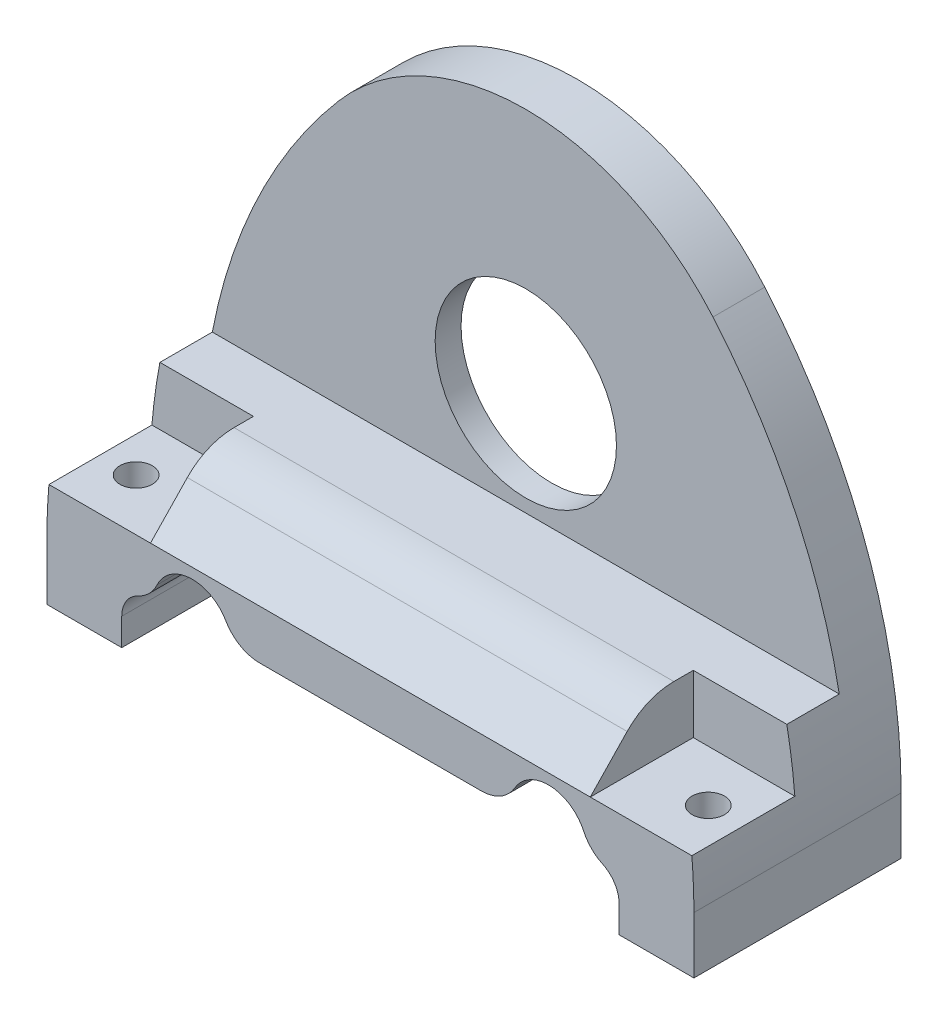
SolidWorks part; units mm, degrees
ref_plane "Plano frontal" through (0, 0, 0) normal (0, 0, 1) x (1, 0, 0)
ref_plane "Plano superior" through (0, 0, 0) normal (0, 1, 0) x (1, 0, 0)
ref_plane "Plano direito" through (0, 0, 0) normal (1, 0, 0) x (0, 0, -1)
sketch "Esboço1" plane through (0, 0, 0) normal (0, 0, 1) x (1, 0, 0)
  line L0 (0, 0) -> (24.98, 0) construction
  line L1 (0, 0) -> (-24.98, 0) construction
  line L2 (0, 0) -> (0, -20.6) construction
  line L3 (-24.98, -20.6) -> (24.98, -20.6) construction
  line L4 (-24.98, -20.6) -> (-24.98, 0)
  line L5 (-24.98, 0) -> (-14.4516, 12.335)
  line L6 (24.98, -20.6) -> (24.98, 0)
  line L7 (24.98, 0) -> (14.4516, 12.335)
  line L11 (18.98, -20.6) -> (24.98, -20.6)
  line L14 (-18.98, -20.6) -> (-24.98, -20.6)
  line L16 (18.98, -20.6) -> (-18.98, -20.6)
  circle A0 centre (0, 0) radius 14.95
  arc A1 (14.4516, 12.335) -> (-14.4516, 12.335) centre (0, 0) ccw
  dimension "D1" = 37.96
  dimension "D2" = 29.9
  dimension "D3" = 38
  dimension "D5" = 20.6
  dimension "D8" = 6
  dimension "D9" = 6
extrude "Ressalto-extrusão1" add sketch "Esboço1" along normal blind 2
sketch "Esboço2" plane through (0, 0, 2) normal (0, 0, 1) x (1, 0, 0)
  line L5 (24.98, 0) -> (14.4516, 12.335)
  line L6 (-14.4516, 12.335) -> (-24.98, 0)
  line L7 (-24.98, 0) -> (-24.98, -20.6)
  line L8 (-24.98, -20.6) -> (24.98, -20.6)
  line L9 (24.98, -20.6) -> (24.98, 0)
  line L10 (24.98, 0) -> (14.4516, 12.335)
  line L11 (-14.4516, 12.335) -> (-24.98, 0)
  line L12 (-24.98, 0) -> (-24.98, -20.6)
  line L13 (-24.98, -20.6) -> (24.98, -20.6)
  line L14 (24.98, -20.6) -> (24.98, 0)
  circle A0 centre (0, 0) radius 7
  arc A1 (14.4516, 12.335) -> (-14.4516, 12.335) centre (0, 0) ccw
  arc A2 (14.4516, 12.335) -> (-14.4516, 12.335) centre (0, 0) ccw
  dimension "D2" = 14
  dimension "D1" = 0
extrude "Ressalto-extrusão2" add sketch "Esboço2" along normal blind 2
sketch "Esboço3" plane through (0, -20.6, 0) normal (0, -1, 0) x (1, 0, 0)
  line L0 (24.98, 4) -> (24.98, 0) construction
  line L1 (-24.98, 4) -> (24.98, 4)
  line L2 (-24.98, 4) -> (-24.98, 16)
  line L3 (-24.98, 16) -> (24.98, 16)
  line L4 (24.98, 4) -> (24.98, 16)
  dimension "D1" = 12
extrude "Ressalto-extrusão3" add sketch "Esboço3" against normal blind 8.1
chamfer "Chanfro1" distance 12 distance2 12.5 1 edges
fillet "Filete1" radius 44 2 edges at (-24.98, 0, 2) (24.98, 0, 2)
sketch "Esboço4" plane through (0, 0, 16) normal (0, 0, 1) x (1, 0, 0)
  line L1 (17, -16.5) -> (-17, -16.5) construction
  line L3 (17, -16.5) -> (-17, -16.5)
  line L4 (19, -18.5) -> (19, -20.6)
  line L5 (-19, -18.5) -> (-19, -20.6)
  line L8 (24.8221, -12.5) -> (-24.8221, -12.5)
  line L9 (-24.98, -16.2247) -> (-24.98, -20.6)
  line L10 (-24.98, -20.6) -> (24.98, -20.6)
  line L11 (24.98, -20.6) -> (24.98, -16.2247)
  line L14 (-19, -20.6) -> (19, -20.6)
  arc A0 (-17, -16.5) -> (-17, -20.5) centre (-17, -18.5) ccw construction
  arc A1 (17, -20.5) -> (17, -16.5) centre (17, -18.5) ccw construction
  arc A2 (-17, -16.5) -> (-19, -18.5) centre (-17, -18.5) ccw
  arc A3 (19, -18.5) -> (17, -16.5) centre (17, -18.5) ccw
  arc A6 (-24.8221, -12.5) -> (-24.98, -16.2247) centre (19.02, -16.2247) ccw
  arc A7 (24.98, -16.2247) -> (24.8221, -12.5) centre (-19.02, -16.2247) ccw
  dimension "D1" = 0
extrude "Corte-extrusão1" cut sketch "Esboço4" against normal up to next
sketch "Esboço6" plane through (0, 0, 0) normal (0, 0, -1) x (-1, 0, 0)
  line L0 (17, -16.3) -> (16.75, -16.3)
  line L1 (-8.5538, -16.3) -> (8.5538, -16.3)
  line L2 (-17, -16.3) -> (-16.75, -16.3)
  line L3 (-13.75, -16.3) -> (13.75, -16.3) construction
  line L4 (0, 0) -> (0, -16.3) construction
  line L5 (-19.2, -20.6) -> (19.2, -20.6)
  line L6 (19.2, -20.6) -> (19.2, -18.5)
  line L7 (17, -16.3) -> (-17, -16.3)
  line L8 (-19.2, -18.5) -> (-19.2, -20.6)
  line L9 (19.2, -20.6) -> (19.2, -18.5)
  line L10 (17, -16.3) -> (-17, -16.3) construction
  line L11 (-19.2, -18.5) -> (-19.2, -20.6)
  arc A0 (-11.1519, -14.8) -> (-16.75, -16.3) centre (-13.75, -16.3) ccw
  arc A1 (16.75, -16.3) -> (11.1519, -14.8) centre (13.75, -16.3) ccw
  arc A3 (-11.1519, -14.8) -> (-8.5538, -16.3) centre (-8.5538, -13.3) ccw
  arc A4 (19.2, -18.5) -> (17, -16.3) centre (17, -18.5) ccw
  arc A5 (-17, -16.3) -> (-19.2, -18.5) centre (-17, -18.5) ccw
  arc A6 (19.2, -18.5) -> (17, -16.3) centre (17, -18.5) ccw
  arc A7 (-17, -16.3) -> (-19.2, -18.5) centre (-17, -18.5) ccw
  arc A8 (11.1519, -14.8) -> (8.5538, -16.3) centre (8.5538, -13.3) cw
  point P19 (-16.75, -16.3)
  point P22 (-10.75, -16.3)
  point P25 (10.75, -16.3)
  point P28 (16.75, -16.3)
  dimension "D3" = 6
  dimension "D4" = 6
  dimension "D5" = 3
  dimension "D2" = 27.5
  dimension "D1" = 0.2
extrude "Corte-extrusão2" cut sketch "Esboço6" against normal through all
ref_plane "Plano1" through (0, 0, 0) normal (0, -1, 0) x (-1, 0, 0)
sketch "Esboço7" plane through (0, 0, 0) normal (0, -1, 0) x (-1, 0, 0)
  line L0 (-7, -4) -> (-21.8794, -4) construction
  line L1 (21.8794, -4) -> (7, -4) construction
  line L2 (-7, -4) -> (-21.8794, -4) construction
  line L3 (21.8794, -4) -> (7, -4) construction
  line L4 (-24.8221, -16) -> (24.8221, -16) construction
  line L5 (-24.8221, -16) -> (24.8221, -16) construction
  line L7 (24.8221, -16) -> (-24.8221, -16)
  line L8 (24.8221, -16) -> (24.8221, -4)
  line L9 (24.8221, -4) -> (-24.8221, -4)
  line L10 (-24.8221, -16) -> (-24.8221, -4)
extrude "Corte-extrusão5" cut sketch "Esboço7" along normal blind 8 contours L10 L7 L8 L9
fillet "Filete2" radius 5 1 edges at (0, -8, 11.68)
sketch "Esboço8" plane through (0, -20.6, 0) normal (0, -1, 0) x (1, 0, 0)
  line L0 (22.09, 0) -> (22.09, 16) construction
  line L1 (19.2, 0) -> (24.98, 0) construction
  line L2 (24.98, 16) -> (19.2, 16) construction
  line L3 (-22.09, 0) -> (-22.09, 16) construction
  line L4 (-24.98, 0) -> (-19.2, 0) construction
  line L5 (-19.2, 16) -> (-24.98, 16) construction
  line L6 (22.09, 4) -> (-22.09, 4) construction
  line L7 (22.09, 12) -> (-22.09, 12) construction
  point P12 (22.09, 4)
  point P13 (-22.09, 4)
  point P14 (22.09, 12)
  point P15 (-22.09, 12)
  dimension "D1" = 4
  dimension "D2" = 4
hole_wizard "Furo roscado de M3x0.51" positions "Esboço10" profile "Esboço9" tap size "M3x0.5" standard "Ansi Metric"
sketch "Esboço10" plane through (0, -20.6, 0) normal (0, -1, 0) x (1, 0, 0)
  point P0 (22.09, 4)
  point P3 (22.09, 12)
  point P6 (-22.09, 4)
  point P9 (-22.09, 12)
sketch "Esboço9" plane through (22.09, -20.6, 4) normal (1, 0, 0) x (0, 0, -1)
  line L0 (0, 0) -> (0, 9.2511)
  line L1 (0, 9.2511) -> (1.25, 8.5)
  line L2 (1.25, 8.5) -> (1.25, 0)
  line L5 (1.25, 0) -> (0, 0)
  line L10 (0, 9.2511) -> (-1.25, 8.5) construction
  line L11 (0, -6.35) -> (0, 107.95) construction
  dimension "Tap Drill Dia." = 2.5
  dimension "Tap Drill Depth" = 8.5
  dimension "Drill Angle" = 118
sketch "Esboço11" plane through (0, 0, 0) normal (1, 0, 0) x (0, 0, -1)
  line L1 (-13.1558, -9.5373) -> (-16, -12.5) construction
  line L4 (-13.1558, -9.5373) -> (-16, -12.5)
  line L6 (-16, -12.5) -> (-9.5489, -12.5)
  line L7 (-9.5489, -12.5) -> (-9.5489, -8)
  arc A0 (-9.5489, -8) -> (-13.1558, -9.5373) centre (-9.5489, -13) ccw construction
  arc A1 (-9.5489, -8) -> (-13.1558, -9.5373) centre (-9.5489, -13) ccw
sketch "Esboço12" plane through (24.98, 0, 0) normal (1, 0, 0) x (0, 0, -1)
  line L0 (-9.5489, -12.5) -> (-8.0489, -12.5)
  line L1 (-8.0489, -12.5) -> (-8.0489, -8)
  line L2 (-8.0489, -8) -> (-9.5489, -8)
  line L3 (-13.1558, -9.5373) -> (-16, -12.5)
  line L4 (-16, -12.5) -> (-9.5489, -12.5)
  line L5 (-9.5489, -12.5) -> (-9.5489, -8)
  line L6 (-13.1558, -9.5373) -> (-16, -12.5)
  line L7 (-16, -12.5) -> (-9.5489, -12.5)
  line L8 (-9.5489, -12.5) -> (-9.5489, -8) construction
  arc A1 (-9.5489, -8) -> (-13.1558, -9.5373) centre (-9.5489, -13) ccw
  arc A2 (-9.5489, -8) -> (-13.1558, -9.5373) centre (-9.5489, -13) ccw
  dimension "D2" = 1.5
  dimension "D1" = 0
extrude "Corte-extrusão6" cut sketch "Esboço12" against normal blind 8
mirror "Espelhar1" about plane through (0, 0, 0) normal (1, 0, 0) of "Corte-extrusão6"
fillet "Filete3" radius 3 2 edges at (16.75, -16.3, 8) (-16.75, -16.3, 8)
